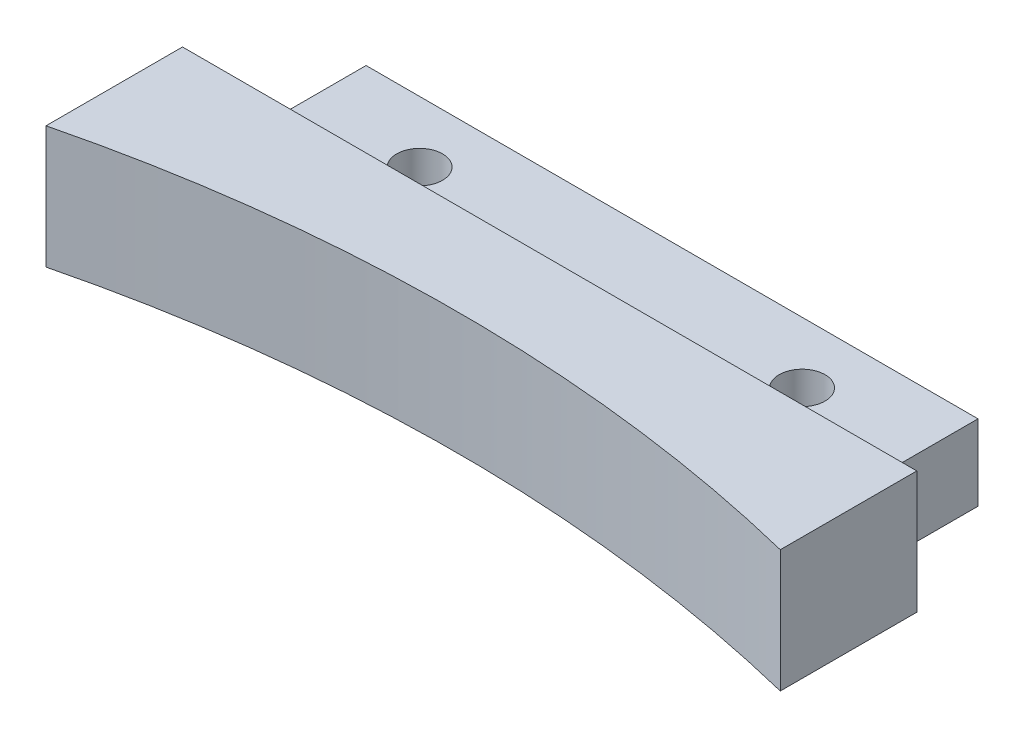
SolidWorks part; units mm, degrees
material "6061-T6 (SS)"
ref_plane "Front Plane" through (0, 0, 0) normal (0, 0, 1) x (1, 0, 0)
ref_plane "Top Plane" through (0, 0, 0) normal (0, 1, 0) x (1, 0, 0)
ref_plane "Right Plane" through (0, 0, 0) normal (1, 0, 0) x (0, 0, -1)
sketch "Sketch1" plane through (0, 0, 0) normal (0, 1, 0) x (1, 0, 0)
  line L0 (-20, 0) -> (0, 0)
  line L1 (24, -8) -> (24, -16.9227)
  line L2 (-24, -8) -> (-24, -16.9227)
  line L3 (-24, -14) -> (24, -14) construction
  line L4 (-20, 0) -> (-20, -8)
  line L5 (-20, -8) -> (-24, -8)
  line L6 (20, 0) -> (20, -8)
  line L7 (20, -8) -> (24, -8)
  line L22 (0, 0) -> (20, 0)
  line L25 (-24, -16.9227) -> (0, -114) construction
  line L26 (0, -114) -> (24, -16.9227) construction
  arc A0 (-24, -16.9227) -> (24, -16.9227) centre (0, -114) cw
  dimension "D1" = 6
  dimension "D2" = 100
  dimension "D3" = 8
  dimension "D4" = 20
  dimension "D5" = 48
extrude "Boss-Extrude1" add sketch "Sketch1" along normal mid plane 8
sketch "Sketch6" plane through (0, 4, 0) normal (0, 1, 0) x (1, 0, 0)
  line L1 (-20, 0) -> (20, 0)
  line L2 (-20, 0) -> (-20, -8)
  line L3 (-20, -8) -> (20, -8)
  line L4 (20, 0) -> (20, -8)
extrude "Cut-Extrude1" cut sketch "Sketch6" against normal blind 3.05
sketch "Sketch10" plane through (0, 0.95, 0) normal (0, 1, 0) x (1, 0, 0)
  line L0 (-20, -4) -> (20, -4) construction
  line L1 (-20, 0) -> (-20, -8) construction
  line L2 (20, -8) -> (20, 0) construction
  circle A0 centre (-12.5, -4) radius 1.5
  circle A1 centre (12.5, -4) radius 1.5
  dimension "D1" = 3
  dimension "D2" = 7.5
  dimension "D3" = 7.5
extrude "Cut-Extrude2" cut sketch "Sketch10" against normal through all
